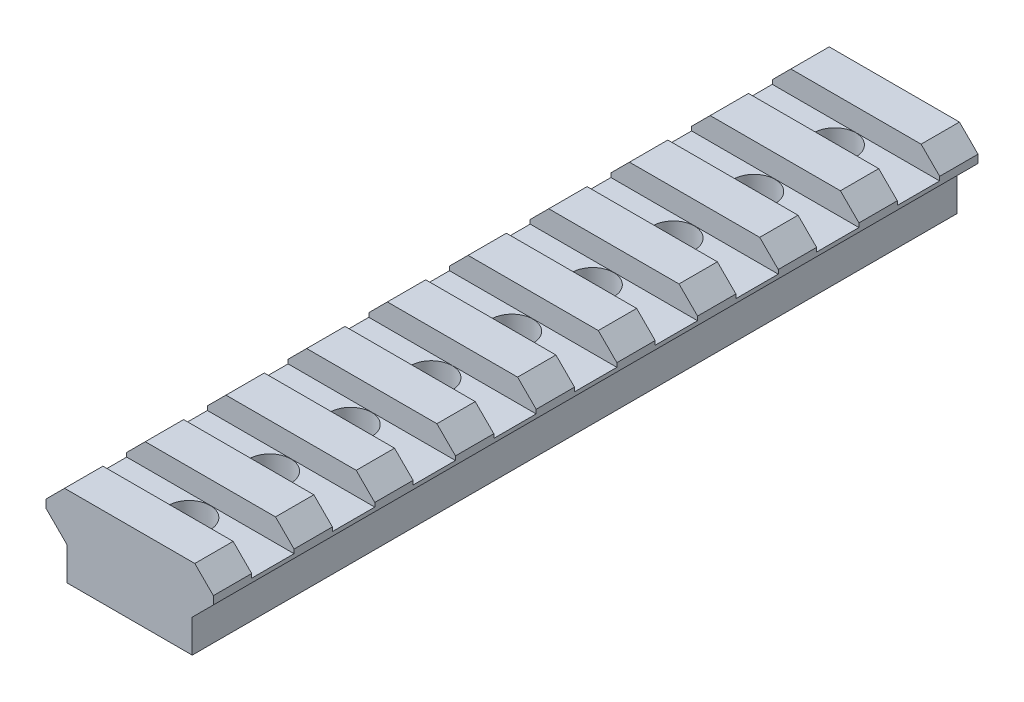
SolidWorks part; units mm, degrees
ref_plane "Płaszczyzna przednia" through (0, 0, 0) normal (0, 0, 1) x (1, 0, 0)
ref_plane "Płaszczyzna górna" through (0, 0, 0) normal (0, 1, 0) x (1, 0, 0)
ref_plane "Płaszczyzna prawa" through (0, 0, 0) normal (1, 0, 0) x (0, 0, -1)
sketch "Szkic1" plane through (0, 0, 0) normal (0, 0, 1) x (1, 0, 0)
  line L0 (2.8, 2.8) -> (0, 0)
  line L5 (3.12, -3.12) -> (18.62, -3.12) construction
  line L6 (1.37, 1.37) -> (20.37, 1.37) construction
  line L7 (0, 0) -> (3.12, -3.12)
  line L8 (18.94, 2.8) -> (21.74, 0)
  line L9 (21.74, 0) -> (18.62, -3.12)
  line L14 (2.8, 2.8) -> (18.94, 2.8)
  line L15 (21.74, 0) -> (0, 0) construction
  line L16 (1.37, 1.37) -> (1.37, -1.37) construction
  line L17 (1.37, -1.37) -> (20.37, -1.37) construction
  line L18 (20.37, 1.37) -> (20.37, -1.37) construction
  line L24 (3.12, -3.12) -> (3.12, -7.2)
  line L25 (3.12, -7.2) -> (18.62, -7.2)
  line L26 (18.62, -7.2) -> (18.62, -3.12)
  dimension "D1" = 19
  dimension "D2" = 45
  dimension "D3" = 15.5
  dimension "D4" = 10
  dimension "D5" = 4.17
  dimension "D6" = 2.74
extrude "Dodanie-wyciągnięcie2" add sketch "Szkic1" along normal blind 94.75
sketch "Szkic2" plane through (0, 2.8, 0) normal (0, 1, 0) x (1, 0, 0)
  line L0 (0, -14.75) -> (0, -20)
  line L6 (0, -94.75) -> (0, 0) construction
  line L7 (0, -4.75) -> (21.74, -4.75)
  line L8 (0, -4.75) -> (0, -10)
  line L9 (0, -10) -> (21.74, -10)
  line L10 (21.74, -4.75) -> (21.74, -10)
  line L11 (21.74, -94.75) -> (21.74, 0) construction
  line L12 (0, -14.75) -> (21.74, -14.75)
  line L14 (21.74, -14.75) -> (21.74, -20)
  line L24 (0, -20) -> (21.74, -20)
  line L26 (0, -24.75) -> (0, -30)
  line L28 (0, -24.75) -> (21.74, -24.75)
  line L30 (21.74, -24.75) -> (21.74, -30)
  line L32 (0, -30) -> (21.74, -30)
  line L34 (0, -34.75) -> (0, -40)
  line L35 (0, -34.75) -> (21.74, -34.75)
  line L60 (21.74, -34.75) -> (21.74, -40)
  line L61 (0, -40) -> (21.74, -40)
  line L62 (0, -44.75) -> (0, -50)
  line L63 (0, -44.75) -> (21.74, -44.75)
  line L64 (21.74, -44.75) -> (21.74, -50)
  line L65 (0, -50) -> (21.74, -50)
  line L66 (0, -54.75) -> (0, -60)
  line L67 (0, -54.75) -> (21.74, -54.75)
  line L68 (21.74, -54.75) -> (21.74, -60)
  line L69 (0, -60) -> (21.74, -60)
  line L70 (0, -64.75) -> (0, -70)
  line L71 (0, -64.75) -> (21.74, -64.75)
  line L72 (21.74, -64.75) -> (21.74, -70)
  line L73 (0, -70) -> (21.74, -70)
  line L74 (0, -74.75) -> (0, -80)
  line L75 (0, -74.75) -> (21.74, -74.75)
  line L76 (21.74, -74.75) -> (21.74, -80)
  line L77 (0, -80) -> (21.74, -80)
  line L78 (0, -84.75) -> (0, -90)
  line L79 (0, -84.75) -> (21.74, -84.75)
  line L80 (21.74, -84.75) -> (21.74, -90)
  line L81 (0, -90) -> (21.74, -90)
  dimension "D1" = 4.75
  dimension "D2" = 5.25
  dimension "D3" = 9
  dimension "D4" = 10
extrude "Wytnij-wyciągnięcie2" cut sketch "Szkic2" against normal blind 2.8
sketch "Szkic3" plane through (0, 0, 0) normal (0, 1, 0) x (1, 0, 0)
  line L0 (10.87, -7.375) -> (10.87, 0) construction
  line L1 (18.94, 0) -> (2.8, 0) construction
  line L2 (21.74, -7.375) -> (10.87, -7.375) construction
  line L3 (21.74, -10) -> (21.74, -4.75) construction
  circle A0 centre (10.87, -7.375) radius 1.3
  circle A9 centre (10.87, -17.375) radius 1.3
  circle A10 centre (10.87, -27.375) radius 1.3
  circle A11 centre (10.87, -37.375) radius 1.3
  circle A12 centre (10.87, -47.375) radius 1.3
  circle A13 centre (10.87, -57.375) radius 1.3
  circle A14 centre (10.87, -67.375) radius 1.3
  circle A15 centre (10.87, -77.375) radius 1.3
  circle A16 centre (10.87, -87.375) radius 1.3
  point P23 (10.87, 0)
  dimension "D2" = 2.6
  dimension "D4" = 10
  dimension "D3" = 9
other "Wyrównaj grupę1"
extrude "Wytnij-wyciągnięcie3" cut sketch "Szkic3" against normal through all
sketch "Szkic4" plane through (0, 0, -1.86) normal (0, -1, 0) x (1, 0, 0)
  circle A0 centre (10.87, 89.235) radius 2.6
  circle A9 centre (10.87, 89.235) radius 1.3 construction
  circle A10 centre (10.87, 79.235) radius 2.6
  circle A11 centre (10.87, 69.235) radius 2.6
  circle A12 centre (10.87, 59.235) radius 2.6
  circle A13 centre (10.87, 49.235) radius 2.6
  circle A14 centre (10.87, 39.235) radius 2.6
  circle A15 centre (10.87, 29.235) radius 2.6
  circle A16 centre (10.87, 19.235) radius 2.6
  circle A17 centre (10.87, 9.235) radius 2.6
  dimension "D1" = 5.2
  dimension "D2" = 9
extrude "Wytnij-wyciągnięcie4" cut sketch "Szkic4" along normal blind 3.2
sketch "Sketch1" plane through (0, 0, 94.75) normal (0, 0, 1) x (1, 0, 0)
  line L0 (10.87, -7.2) -> (10.87, 10.5404) construction
  line L1 (0.5, 0.5) -> (0.5, -0.5)
  line L3 (3.12, -7.2) -> (18.62, -7.2) construction
  line L7 (21.24, 0.5) -> (21.24, -0.5)
  line L8 (18.94, 2.8) -> (2.8, 2.8)
  line L9 (2.8, 2.8) -> (0, 0)
  line L10 (0, 0) -> (3.12, -3.12)
  line L11 (3.12, -3.12) -> (3.12, -7.2)
  line L12 (3.12, -7.2) -> (18.62, -7.2)
  line L14 (18.62, -3.12) -> (21.74, 0)
  line L15 (21.74, 0) -> (18.94, 2.8)
  line L17 (0.5, 0.5) -> (0, 0)
  line L18 (0, 0) -> (0.5, -0.5)
  line L24 (21.74, 0) -> (21.24, -0.5)
  line L25 (21.24, 0.5) -> (21.74, 0)
  line L32 (18.62, -7.2) -> (18.62, -3.12)
  point P17 (0, 0)
  dimension "D1" = 0
extrude "Cut-Extrude1" cut sketch "Sketch1" against normal through all
